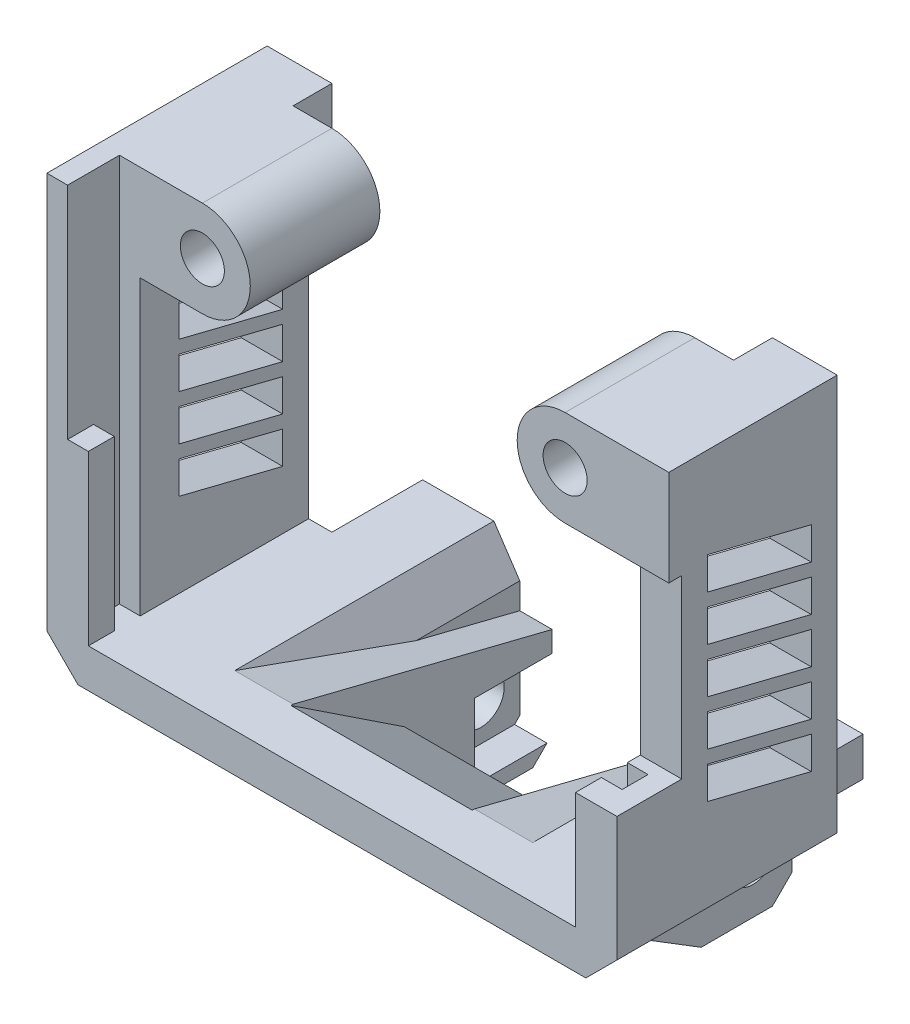
SolidWorks part; units mm, degrees
ref_plane "Спереди" through (0, 0, 0) normal (0, 0, 1) x (1, 0, 0)
ref_plane "Сверху" through (0, 0, 0) normal (0, 1, 0) x (1, 0, 0)
ref_plane "Справа" through (0, 0, 0) normal (1, 0, 0) x (0, 0, -1)
sketch "Эскиз1" plane through (0, 0, 0) normal (0, 0, 1) x (1, 0, 0)
  line L1 (22, 44) -> (-22, 44)
  line L2 (22, 44) -> (22, 10)
  line L3 (22, 10) -> (-22, 10)
  line L4 (-22, 44) -> (-22, 10)
  line L5 (22, 44) -> (-22, 10) construction
  line L6 (22, 10) -> (-22, 44) construction
  point P0 (0, 27)
  dimension "D1" = 10
  dimension "D2" = 44
  dimension "D3" = 44
extrude "Бобышка-Вытянуть1" add sketch "Эскиз1" along normal blind 24
sketch "Эскиз2" plane through (0, 44, 0) normal (0, 1, 0) x (1, 0, 0)
  line L0 (0, 0) -> (0, -24) construction
  line L1 (22, 0) -> (-22, 0) construction
  line L2 (-18.8, 0) -> (18.8, 0)
  line L3 (-18.8, 0) -> (-18.8, -20)
  line L4 (-20.4, -22) -> (-20.4, -20)
  line L5 (18.8, 0) -> (18.8, -20)
  line L6 (-22, -24) -> (-22, 0) construction
  line L7 (22, -24) -> (-22, -24) construction
  line L8 (-18.8, -24) -> (18.8, -24)
  line L9 (-18.8, -24) -> (-18.8, -22)
  line L10 (-18.8, -20) -> (-20.4, -20)
  line L11 (18.8, -24) -> (18.8, -22)
  line L12 (18.8, -22) -> (20.4, -22)
  line L13 (-18.8, -22) -> (-20.4, -22)
  line L14 (18.8, -20) -> (20.4, -20)
  line L15 (20.4, -22) -> (20.4, -20)
  line L16 (22, -24) -> (22, 0) construction
  point P6 (0, 0)
  point P16 (0, -24)
  dimension "D1" = 1.6
  dimension "D2" = 3.2
  dimension "D3" = 2
  dimension "D4" = 20
extrude "Вырез-Вытянуть1" cut sketch "Эскиз2" against normal blind 31
sketch "Эскиз5" plane through (0, 0, 0) normal (0, 0, -1) x (-1, 0, 0)
  line L0 (22, 10) -> (-22, 10) construction
  line L1 (-11.5, 10) -> (11.5, 10)
  line L2 (-11.5, 10) -> (-11.5, -0.5)
  line L3 (-11.5, -0.5) -> (11.5, -0.5)
  line L4 (11.5, 10) -> (11.5, -0.5)
  point P6 (0, -0.5)
  dimension "D1" = 23
  dimension "D2" = 10.5
extrude "Бобышка-Вытянуть4" add sketch "Эскиз5" along normal blind 1 separate body
sketch "Эскиз6" plane through (11.5, 0, 0) normal (1, 0, 0) x (0, 0, -1)
  line L0 (0, -0.5) -> (-7, -0.5)
  line L1 (-24, 10) -> (0, 10)
  line L2 (0, 10) -> (0, -0.5)
  line L3 (-7, -0.5) -> (-24, 10)
  dimension "D1" = 7
extrude "Бобышка-Вытянуть5" add sketch "Эскиз6" against normal up to surface (23 mm away) up to face at (-11.5, 4.75, -0.5)
sketch "Эскиз7" plane through (-11.5, 0, 0) normal (-1, 0, 0) x (0, 0, 1)
  line L1 (24, 10) -> (0, 10) construction
  line L2 (0, 44) -> (0, 10) construction
  circle A0 centre (3, 3.5) radius 1.8
  dimension "D1" = 3.6
  dimension "D2" = 6.5
  dimension "D3" = 3
extrude "Вырез-Вытянуть2" cut sketch "Эскиз7" against normal up to surface (23 mm away) up to face at (11.5, 5.8, 5.8)
ref_plane "Плоскость1" through (-9.5, 0, 0) normal (-1, 0, 0) x (0, 0, 1)
sketch "Эскиз8" plane through (-9.5, 0, 0) normal (-1, 0, 0) x (0, 0, 1)
  line L0 (0, 8) -> (20, 13)
  line L1 (20, 13) -> (0, 13)
  line L2 (0, 13) -> (0, 8)
  dimension "D1" = 5
extrude "Вырез-Вытянуть4" cut sketch "Эскиз8" against normal offset from surface (19 mm away) 2 up to face at (11.5, 1.7, 3)
chamfer "Фаска2" distance 2 distance2 3 1 edges at (9.5, 13, 10) first distance on face at (0, 13, 16)
sketch "Эскиз11" plane through (0, 0, 0) normal (0, 0, -1) x (-1, 0, 0)
  line L0 (-22, 44) -> (-18.8, 44) construction
  line L1 (-14, 43) -> (-18.8, 43)
  line L2 (-18.8, 13) -> (-18.8, 44) construction
  line L3 (-18.8, 43) -> (-18.8, 35.6)
  line L4 (-18.8, 35.6) -> (-14, 35.6)
  line L5 (0, 0) -> (0, 30) construction
  line L6 (18.8, 35.6) -> (14, 35.6)
  line L7 (18.8, 43) -> (18.8, 35.6)
  line L8 (14, 43) -> (18.8, 43)
  circle A0 centre (-14, 39.3) radius 1.7
  arc A1 (-14, 35.6) -> (-14, 43) centre (-14, 39.3) ccw
  arc A2 (14, 35.6) -> (14, 43) centre (14, 39.3) cw
  circle A3 centre (-14, 39.3) radius 3.7 construction
  circle A4 centre (14, 39.3) radius 1.7
  point P11 (-10.3, 30)
  dimension "D1" = 14
  dimension "D3" = 3.4
  dimension "D2" = 4.7
  dimension "D4" = 2
extrude "Бобышка-Вытянуть6" add sketch "Эскиз11" against normal up to surface (20 mm away) up to face at (19.6, 28.5, 20)
sketch "Эскиз13" plane through (-22, 0, 0) normal (-1, 0, 0) x (0, 0, 1)
  line L0 (0, 44) -> (0, 10) construction
  line L1 (9, 34) -> (17, 36)
  line L2 (9, 34) -> (9, 31.5)
  line L3 (9, 31.5) -> (17, 33.5)
  line L4 (17, 36) -> (17, 33.5)
  line L5 (24, 44) -> (0, 44) construction
  line L6 (0, 14) -> (24, 14) construction
  line L7 (24, 44) -> (24, 10) construction
  line L8 (9, 30.5) -> (17, 32.5)
  line L9 (9, 30.5) -> (9, 28)
  line L10 (9, 28) -> (17, 30)
  line L11 (17, 32.5) -> (17, 30)
  line L12 (9, 27) -> (17, 29)
  line L13 (9, 27) -> (9, 24.5)
  line L14 (9, 24.5) -> (17, 26.5)
  line L15 (17, 29) -> (17, 26.5)
  line L16 (9, 23.5) -> (17, 25.5)
  line L17 (9, 23.5) -> (9, 21)
  line L18 (9, 21) -> (17, 23)
  line L19 (17, 25.5) -> (17, 23)
  line L20 (9, 20) -> (17, 22)
  line L21 (9, 20) -> (9, 17.5)
  line L22 (9, 17.5) -> (17, 19.5)
  line L23 (17, 22) -> (17, 19.5)
  dimension "D1" = 2.5
  dimension "D2" = 8
  dimension "D3" = 7
  dimension "D4" = 10
  dimension "D5" = 8
  dimension "D6" = 30
  dimension "D7" = 5
extrude "Вырез-Вытянуть7" cut sketch "Эскиз13" against normal blind 4
mirror "Зеркальное отражение1" about plane through (0, 0, 0) normal (1, 0, 0) of "Вырез-Вытянуть7"
chamfer "Фаска3" distance 2.4 angle 45 2 edges at (-22, 10, 12) (22, 10, 12)
sketch "Эскиз14" plane through (0, 44, 0) normal (0, 1, 0) x (1, 0, 0)
  line L0 (22, -24) -> (18.8, -24) construction
  line L1 (-20.4, -20) -> (20.4, -20)
  line L2 (-20.4, -20) -> (-20.4, -24)
  line L3 (-20.4, -24) -> (20.4, -24)
  line L4 (20.4, -20) -> (20.4, -24)
extrude "Вырез-Вытянуть8" cut sketch "Эскиз14" against normal blind 18
sketch "Эскиз15" plane through (0, 0, 0) normal (0, 0, -1) x (-1, 0, 0)
  line L0 (-22, 12.4) -> (-22, 44) construction
  line L1 (-22, 43) -> (22, 43)
  line L2 (-22, 43) -> (-22, 44)
  line L3 (-22, 44) -> (22, 44)
  line L4 (22, 43) -> (22, 44)
  line L5 (18.8, 44) -> (22, 44) construction
extrude "Вырез-Вытянуть9" cut sketch "Эскиз15" against normal up to surface (24 mm away) up to face at (0, 23.175, 24)
sketch "Эскиз16" plane through (0, 0, 24) normal (0, 0, 1) x (1, 0, 0)
  line L0 (18.8, 13) -> (18.8, 26) construction
  line L1 (18.8, 22) -> (22, 22)
  line L2 (18.8, 22) -> (18.8, 35.6)
  line L3 (18.8, 35.6) -> (22, 35.6)
  line L4 (22, 22) -> (22, 35.6)
  line L5 (22, 12.4) -> (22, 43) construction
  line L6 (11.5, 10) -> (19.6, 10) construction
  line L7 (14, 35.6) -> (18.8, 35.6) construction
  point P10 (15.55, 10)
  dimension "D1" = 12
extrude "Вырез-Вытянуть10" cut sketch "Эскиз16" against normal blind 5
sketch "Эскиз17" plane through (0, 43, 0) normal (0, 1, 0) x (1, 0, 0)
  line L1 (20.4, -20) -> (22, -20)
  line L2 (20.4, -20) -> (20.4, -24)
  line L3 (20.4, -24) -> (22, -24)
  line L4 (22, -20) -> (22, -24)
extrude "Вырез-Вытянуть11" cut sketch "Эскиз17" against normal up to surface (7.4 mm away) up to face at (18.6667, 35.6, 15.9)
sketch "Эскиз18" plane through (0, 0, 0) normal (0, 0, -1) x (-1, 0, 0)
  line L0 (-14, 43) -> (-22, 43) construction
  line L2 (0, 0) -> (0, 43) construction
  line L4 (-22, 43) -> (-17, 43)
  line L5 (-17, 43) -> (-17, 10)
  line L6 (19.6, 10) -> (11.5, 10) construction
  line L7 (-22, 43) -> (-22, 12.4)
  line L8 (-19.6, 10) -> (-17, 10)
  line L10 (-11.5, 10) -> (-19.6, 10) construction
  line L11 (-22, 12.4) -> (-19.6, 10)
  line L12 (22, 12.4) -> (19.6, 10)
  line L13 (17, 43) -> (17, 10)
  line L14 (19.6, 10) -> (17, 10)
  line L15 (22, 43) -> (22, 12.4)
  line L16 (22, 43) -> (17, 43)
  dimension "D1" = 5
extrude "Вырез-Вытянуть12" cut sketch "Эскиз18" against normal blind 7
sketch "Эскиз19" plane through (-11.5, 0, 0) normal (-1, 0, 0) x (0, 0, 1)
  line L1 (0, 10) -> (-1, 10)
  line L2 (0, 10) -> (0, -0.5)
  line L3 (0, -0.5) -> (-1, -0.5)
  line L4 (-1, 10) -> (-1, -0.5)
extrude "Вырез-Вытянуть13" cut sketch "Эскиз19" against normal up to surface (23 mm away) up to face at (11.5, 1.7, 3)
chamfer "Фаска4" distance 1.5 angle 45 1 edges at (0, -0.5, 0)
chamfer "Фаска5" distance 3 distance2 2 1 edges at (-9.5, 13, 10) first distance on face at (-9.5, 11.3333, 6.6667)
sketch "Эскиз20" plane through (0, 0, 0) normal (0, 1, 0) x (1, 0, 0)
  line L0 (-6.5, -1.57) -> (-6.5, -10.07) construction
  line L1 (6.5, -10.07) -> (-6.5, -10.07) construction
  line L2 (6.5, -10.07) -> (6.5, 0.8866) construction
  line L3 (6.5, 0.8866) -> (-6.5, 0.8866) construction
  line L4 (-6.5, -10.07) -> (-6.5, 0.8866) construction
  line L5 (-7, -10.57) -> (-7, 1.3866)
  line L6 (7, 1.3866) -> (-7, 1.3866)
  line L7 (7, -10.57) -> (7, 1.3866)
  line L8 (7, -10.57) -> (-7, -10.57)
  dimension "D1" = 0.5
extrude "Вырез-Вытянуть14" cut sketch "Эскиз20" along normal blind 17 from offset 3 offset against normal yes
chamfer "Фаска6" distance 10 distance2 4 1 edges at (0, 10.6425, 10.57) first distance on face at (0, 9.9285, 7.714)
chamfer "Фаска7" distance 1 distance2 1 2 edges at (0, 1.705, 10.57) (0, 6.6425, 10.57)
ref_plane "Плоскость2" through (-22, 43, 7) normal (0, 0, -1) x (-1, 0, 0)
sketch "Эскиз22" plane through (0, 43, 0) normal (0, 1, 0) x (1, 0, 0)
  line L0 (10.3, 0) -> (10.3, -20) construction
  line L2 (10.3, -10) -> (17, -10)
  line L3 (10.3, -10) -> (10.3, 0)
  line L4 (10.3, 0) -> (17, 0)
  line L5 (0, 0) -> (0, -29.9114) construction
  line L6 (17, -10) -> (17, 0)
  line L8 (-10.3, 0) -> (-17, 0)
  line L9 (-17, -10) -> (-17, 0)
  line L10 (-10.3, -10) -> (-17, -10)
  line L11 (-10.3, -10) -> (-10.3, 0)
extrude "Вырез-Вытянуть15" cut sketch "Эскиз22" against normal blind 10
sketch "Эскиз24" plane through (-7, 0, 0) normal (1, 0, 0) x (0, 0, -1)
  line L1 (0, 0.6) -> (-6, 0.6)
  line L2 (0, 0.6) -> (0, 6.4)
  line L3 (0, 6.4) -> (-6, 6.4)
  line L4 (-6, 0.6) -> (-6, 6.4)
  line L5 (0, 0.6) -> (-6, 6.4) construction
  line L6 (0, 6.4) -> (-6, 0.6) construction
  point P0 (-3, 3.5)
  dimension "D1" = 6
  dimension "D2" = 5.8
extrude "Вырез-Вытянуть16" cut sketch "Эскиз24" against normal blind 2.5
mirror "Зеркальное отражение2" about plane through (0, 0, 0) normal (1, 0, 0) of "Вырез-Вытянуть16"
